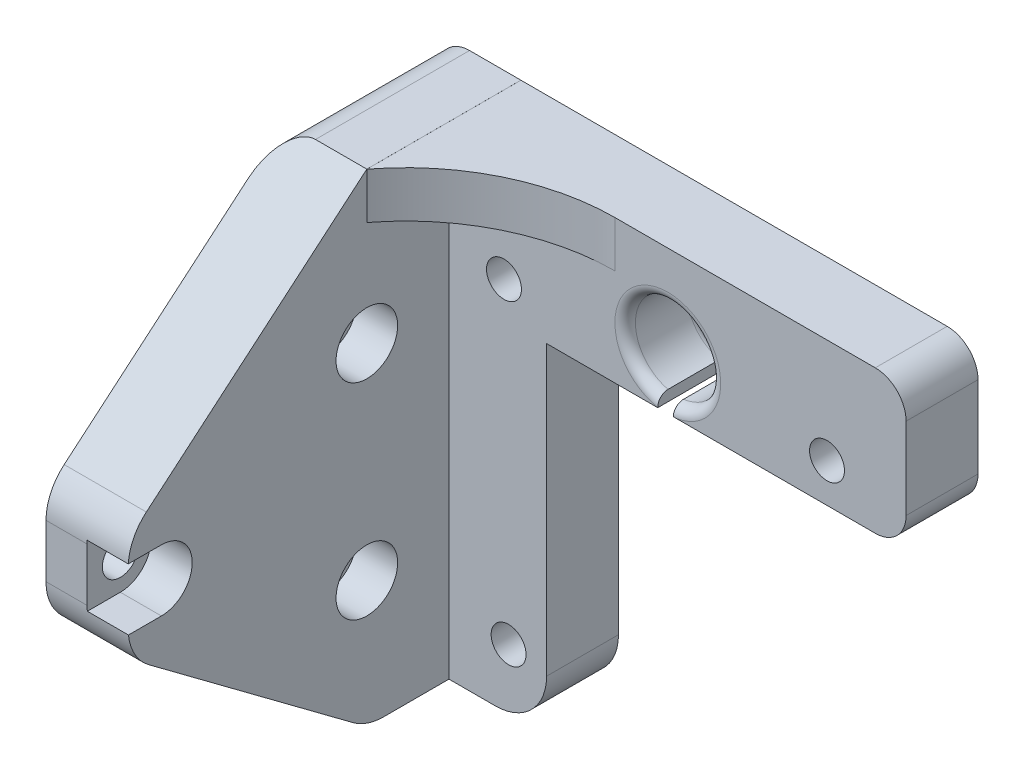
SolidWorks part; units mm, degrees
material "ABS"
ref_plane "Front Plane" through (0, 0, 0) normal (0, 0, 1) x (1, 0, 0)
ref_plane "Top Plane" through (0, 0, 0) normal (0, 1, 0) x (1, 0, 0)
ref_plane "Right Plane" through (0, 0, 0) normal (1, 0, 0) x (0, 0, -1)
ref_plane "Plane5" through (60, 0, 0) normal (1, 0, 0) x (0, 0, -1)
sketch "Sketch50" plane through (60, 0, 0) normal (1, 0, 0) x (0, 0, -1)
  line L0 (-38.2349, -28) -> (-38.2349, -38)
  line L1 (0, -55.3249) -> (-15, -55.3249)
  line L2 (0, -8.3249) -> (-15, -8.3249)
  line L4 (0, -55.3249) -> (0, -8.3249)
  line L5 (-15, -2.0171) -> (-15, -57.8143) construction
  line L9 (-38.2349, -28) -> (-15, -8.3249)
  line L10 (-38.2349, -38) -> (-15, -55.3249)
  circle A0 centre (-35, -33) radius 1.75
  circle A1 centre (-15, -23) radius 1.75
  circle A2 centre (-15, -43) radius 1.75
  dimension "D1" = 3.5
  dimension "D2" = 3.5
  dimension "D3" = 3.5
  dimension "D4" = 20
  dimension "D5" = 20
  dimension "D6" = 47
  dimension "D7" = 15
  dimension "D8" = 10
extrude "Extrude1" add sketch "Sketch50" along normal blind 8 separate body
sketch "Sketch52" plane through (0, 0, 0) normal (0, 0, -1) x (-1, 0, 0)
  line L0 (-61.5211, -55.3284) -> (-61.5211, -8.3284)
  line L1 (-112.5, -8.3284) -> (-112.5, -22.2806)
  line L2 (-61.5211, -8.3284) -> (-112.5, -8.3284)
  line L3 (-77.5, -22.2806) -> (-112.5, -22.2806)
  line L4 (-61.5211, -55.3284) -> (-77.5, -55.3284)
  line L5 (-77.5, -55.3249) -> (-77.5, -8.3249)
  line L6 (-77.5, -55.3284) -> (-77.5, -22.2806)
  circle A0 centre (-89.3, -17.2) radius 4.15
  circle A1 centre (-73.3515, -18.9313) radius 1.7
  circle A2 centre (-104.8, -18.5) radius 1.7
  circle A3 centre (-73.8015, -49.5086) radius 1.7
  point P3 (-113, -87.5802)
  point P9 (-74.0211, -54.9585)
  point P10 (-74.0211, -7.7617)
  dimension "D2" = 47
  dimension "D4" = 3.4
  dimension "D3" = 8.3
  dimension "D5" = 15.9789
  dimension "D1" = 9.5
extrude "Extrude2" add sketch "Sketch52" against normal blind 7
fillet "Fillet1" radius 3 2 edges at (112.5, -22.2806, 3.5) (112.5, -8.3284, 3.5)
fillet "Fillet2" radius 5 1 edges at (77.5, -55.3284, 3.5)
sketch "Sketch54" plane through (0, -8.3284, 0) normal (0, 1, 0) x (1, 0, 0)
  line L0 (68, -7) -> (109.5, -7) construction
  line L1 (68, -15) -> (68, -7)
  line L2 (68, -15) -> (68, -38.2349) construction
  line L3 (68, 0) -> (68, -15) construction
  line L4 (68, -7) -> (84.1795, -7)
  arc A0 (84.1795, -7) -> (68, -15) centre (84.1795, -27.3609) ccw
extrude "Extrude3" add sketch "Sketch54" against normal blind 4.5
fillet "Fillet4" radius 5 3 edges at (64, -28, 38.2349) (64, -38, 38.2349) (64, -55.3249, 15)
fillet "Fillet5" radius 3 1 edges at (60, -8.3249, 7.5)
sketch "Sketch55" plane through (68, 0, 0) normal (1, 0, 0) x (0, 0, -1)
  line L0 (-35, -30) -> (-38.7879, -30)
  line L1 (-38.7879, -30) -> (-38.7879, -36)
  line L2 (-35, -36) -> (-38.7879, -36)
  arc A0 (-35, -36) -> (-35, -30) centre (-35, -33) ccw
  circle A1 centre (-15, -23) radius 3
  circle A2 centre (-15, -43) radius 3
  dimension "D1" = 6
  dimension "D2" = 6
  dimension "D3" = 6
extrude "Cut-Extrude3" cut sketch "Sketch55" against normal blind 4
sketch "Sketch56" plane through (0, 0, 0) normal (0, 0, -1) x (-1, 0, 0)
  line L0 (-109.5, -22.2806) -> (-77.5, -22.2806) construction
  line L1 (-89.3173, -23.6005) -> (-88.3204, -23.6005)
  line L2 (-89.3173, -23.6005) -> (-89.3173, -20.9607)
  line L3 (-89.3173, -20.9607) -> (-88.3204, -20.9607)
  line L4 (-88.3204, -23.6005) -> (-88.3204, -20.9607)
  line L5 (-89.3173, -23.6005) -> (-88.3204, -20.9607) construction
  line L6 (-89.3173, -20.9607) -> (-88.3204, -23.6005) construction
  point P0 (-88.8189, -22.2806)
fillet "Fillet9" radius 1 1 edges at (89.3, -13.05, 0)
fillet "Fillet10" radius 1 1 edges at (89.3, -13.05, 7)
sketch "Sketch57" plane through (0, -22.2806, 0) normal (0, -1, 0) x (1, 0, 0)
  line L0 (88.8276, 7.5275) -> (89.8276, 7.5275)
  line L2 (89.8276, -0.6284) -> (89.8276, 7.5275)
  line L3 (88.8276, -0.6284) -> (88.8276, 7.5275)
  line L4 (88.8276, -0.6284) -> (89.8276, -0.6284)
extrude "Extrude4" cut sketch "Sketch57" against normal blind 4
extrude "Cut-Extrude4" cut sketch "Sketch56" against normal up to surface (7 mm away) up to face at (85.3186, -28.299, 7)
